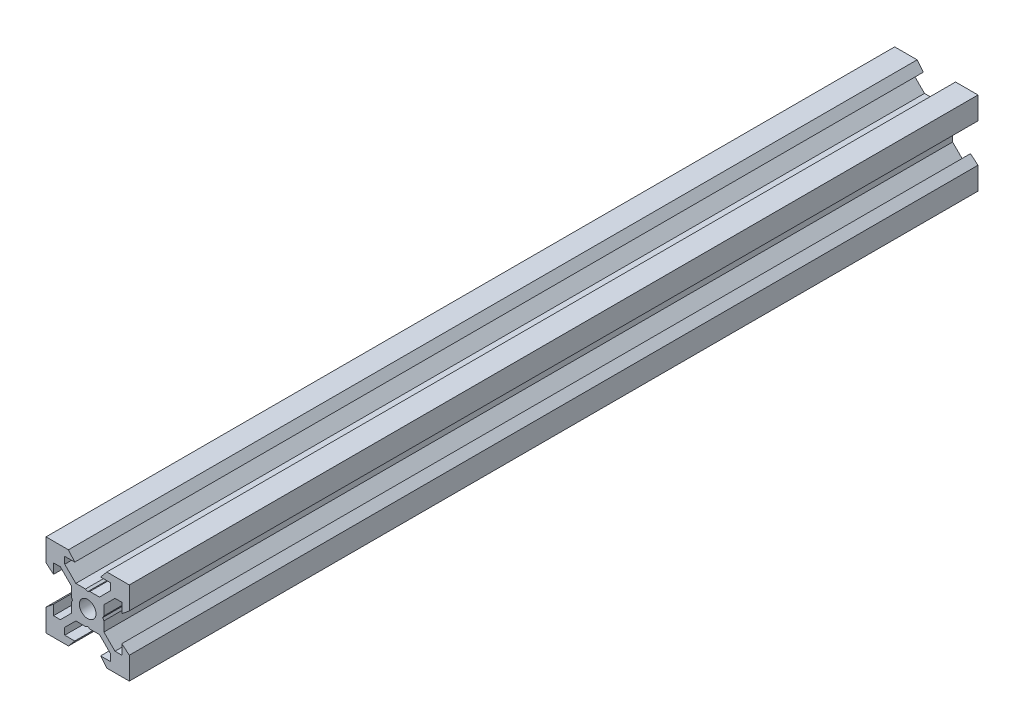
SolidWorks part; units mm, degrees
ref_plane "Front Plane" through (0, 0, 0) normal (0, 0, 1) x (1, 0, 0)
ref_plane "Top Plane" through (0, 0, 0) normal (0, 1, 0) x (1, 0, 0)
ref_plane "Right Plane" through (0, 0, 0) normal (1, 0, 0) x (0, 0, -1)
sketch "Sketch1" plane through (0, 0, 0) normal (0, 0, 1) x (1, 0, 0)
  line L0 (10, 10) -> (4.6104, 10) construction
  line L1 (10, 10) -> (10, 4.6104) construction
  line L2 (10, -10) -> (10, -4.6104) construction
  line L3 (10, -10) -> (4.6104, -10) construction
  line L4 (10, 10) -> (10, 4.6104)
  line L5 (6.5607, 5.5) -> (8.2, 5.5)
  line L6 (5.5, 8.2) -> (5.5, 6.5607)
  line L7 (10, 10) -> (4.6104, 10)
  line L8 (10, 10) -> (10, 4.6104)
  line L9 (6.5607, 5.5) -> (3.9, 2.8393)
  line L10 (5.5, 6.5607) -> (2.8393, 3.9)
  line L11 (10, 4.6104) -> (8.2, 3.1)
  line L12 (4.6104, 10) -> (3.1, 8.2)
  line L13 (8.2, 3.1) -> (8.2, 5.5)
  line L14 (3.1, 8.2) -> (5.5, 8.2)
  line L15 (-6.5607, 5.5) -> (-8.2, 5.5)
  line L16 (6.5607, -5.5) -> (8.2, -5.5)
  line L17 (3.1, -8.2) -> (5.5, -8.2)
  line L18 (8.2, -3.1) -> (8.2, -5.5)
  line L19 (4.6104, -10) -> (3.1, -8.2)
  line L20 (10, -4.6104) -> (8.2, -3.1)
  line L21 (0.5196, -3.9) -> (0, -3.6)
  line L22 (0.5196, 3.9) -> (0, 3.6)
  line L23 (3.6, 0) -> (3.9, -0.5196)
  line L24 (3.9, 0.5196) -> (3.6, 0)
  line L25 (3.9, 0.5196) -> (3.9, 2.8393)
  line L26 (2.8393, 3.9) -> (0.5196, 3.9)
  line L27 (3.9, -2.8393) -> (3.9, -0.5196)
  line L28 (2.8393, -3.9) -> (0.5196, -3.9)
  line L29 (5.5, -6.5607) -> (2.8393, -3.9)
  line L30 (6.5607, -5.5) -> (3.9, -2.8393)
  line L31 (10, -10) -> (10, -4.6104)
  line L32 (10, -10) -> (4.6104, -10)
  line L33 (5.5, -8.2) -> (5.5, -6.5607)
  line L34 (-6.5607, -5.5) -> (-8.2, -5.5)
  line L35 (10, -10) -> (10, -4.6104)
  line L36 (0, 0) -> (0, 8.2) construction
  line L37 (-10, -10) -> (-4.6104, -10) construction
  line L38 (-10, -10) -> (-10, -4.6104) construction
  line L39 (-10, 10) -> (-10, 4.6104) construction
  line L40 (-10, 10) -> (-4.6104, 10) construction
  line L41 (-10, -10) -> (-10, -4.6104)
  line L43 (-5.5, -8.2) -> (-5.5, -6.5607)
  line L44 (-10, -10) -> (-4.6104, -10)
  line L45 (-10, -10) -> (-10, -4.6104)
  line L46 (-6.5607, -5.5) -> (-3.9, -2.8393)
  line L47 (-5.5, -6.5607) -> (-2.8393, -3.9)
  line L48 (-2.8393, -3.9) -> (-0.5196, -3.9)
  line L49 (-3.9, -2.8393) -> (-3.9, -0.5196)
  line L50 (-2.8393, 3.9) -> (-0.5196, 3.9)
  line L51 (-3.9, 0.5196) -> (-3.9, 2.8393)
  line L52 (-3.9, 0.5196) -> (-3.6, 0)
  line L53 (-3.6, 0) -> (-3.9, -0.5196)
  line L54 (-0.5196, 3.9) -> (0, 3.6)
  line L55 (-0.5196, -3.9) -> (0, -3.6)
  line L56 (-10, -4.6104) -> (-8.2, -3.1)
  line L57 (-4.6104, -10) -> (-3.1, -8.2)
  line L58 (-8.2, -3.1) -> (-8.2, -5.5)
  line L59 (-3.1, -8.2) -> (-5.5, -8.2)
  line L60 (-10, -10) -> (10, -10) construction
  line L61 (-10, -10) -> (-10, 10) construction
  line L62 (-3.1, 8.2) -> (-5.5, 8.2)
  line L63 (-8.2, 3.1) -> (-8.2, 5.5)
  line L64 (-4.6104, 10) -> (-3.1, 8.2)
  line L65 (-10, 4.6104) -> (-8.2, 3.1)
  line L66 (-5.5, 6.5607) -> (-2.8393, 3.9)
  line L67 (-6.5607, 5.5) -> (-3.9, 2.8393)
  line L68 (-10, 10) -> (-10, 4.6104)
  line L69 (-10, 10) -> (-4.6104, 10)
  line L70 (-5.5, 8.2) -> (-5.5, 6.5607)
  line L71 (-10, 10) -> (10, 10) construction
  line L72 (-10, 10) -> (-10, 4.6104)
  line L73 (10, -10) -> (10, 10) construction
  line L74 (-10, -10) -> (10, 10) construction
  line L75 (-10, 10) -> (10, -10) construction
  circle A0 centre (0, 0) radius 2
  dimension "D7" = 4
  dimension "D1" = 20
  dimension "D2" = 5.3896
  dimension "D3" = 4.5
  dimension "D4" = 50
  dimension "D5" = 1.8
  dimension "D6" = 1.5104
  dimension "D8" = 5.5
  dimension "D9" = 120
  dimension "D10" = 0.3
  dimension "D11" = 2.3197
  dimension "D12" = 7.8
  dimension "D13" = 7.8
  dimension "D14" = 1.5
  dimension "D15" = 2.6607
extrude "Boss-Extrude1" add sketch "Sketch1" along normal mid plane 203.74 contours L70 L62 L64 L69 L68 L65 L63 L15 L67 L51 L52 L53 L49 L46 L34 L58 L56 L41 L44 L57 L59 L43 L47 L48 L55 L21 L28 L29 L33 L17 L19 L32 L31 L20 L18 L16 L30 L27 L23 L24 L25 L9 L5 L13 L11 L4 L7 L12 L14 L6 L10 region at (9.7172, 7.3052, 0)
